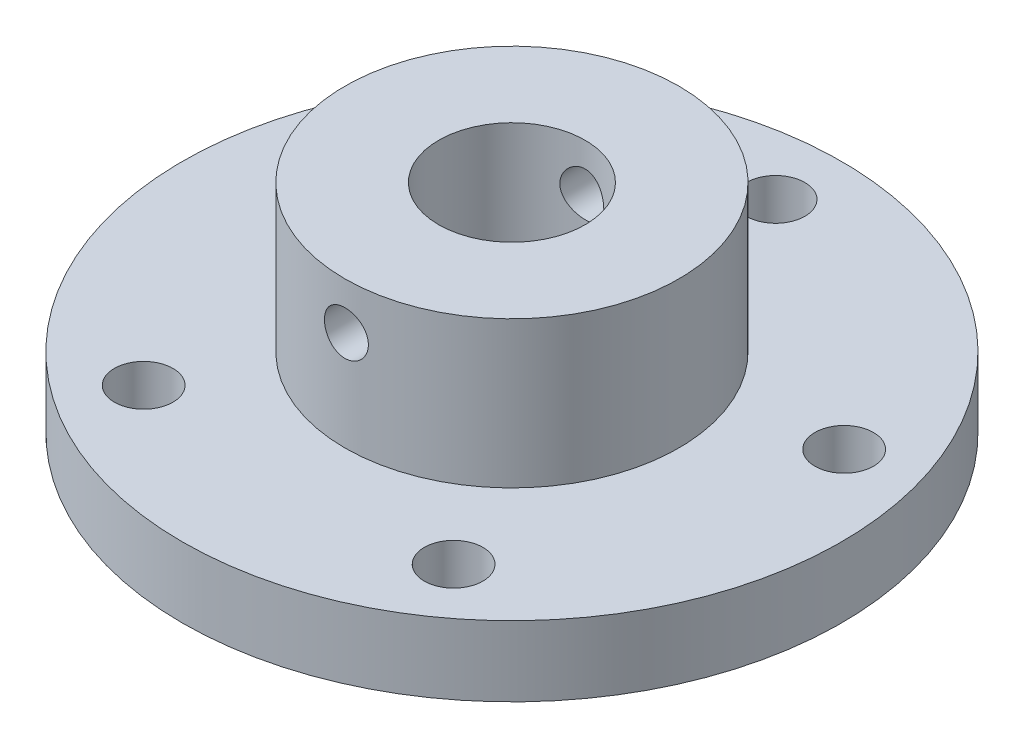
SolidWorks part; units mm, degrees
material "Delrin 2700 NC010, Low Viscosity Acetal Copolymer (SS)"
ref_plane "Front Plane" through (0, 0, 0) normal (0, 0, 1) x (1, 0, 0)
ref_plane "Top Plane" through (0, 0, 0) normal (0, 1, 0) x (1, 0, 0)
ref_plane "Right Plane" through (0, 0, 0) normal (1, 0, 0) x (0, 0, -1)
sketch "Sketch1" plane through (0, 0, 0) normal (0, 0, 1) x (1, 0, 0)
  line L0 (0, 7.8095) -> (0, 0) construction
  line L1 (0, 0) -> (15.875, 0) construction
  line L3 (15.875, 0) -> (71.4375, 0)
  line L4 (15.875, 0) -> (15.875, 15.24)
  line L5 (15.875, 15.24) -> (71.4375, 15.24)
  line L6 (71.4375, 0) -> (71.4375, 15.24)
  line L7 (15.875, 15.24) -> (36.195, 15.24)
  line L8 (15.875, 15.24) -> (15.875, 46.99)
  line L9 (15.875, 46.99) -> (36.195, 46.99)
  line L10 (36.195, 15.24) -> (36.195, 46.99)
  dimension "D1" = 15.875
  dimension "D2" = 15.24
  dimension "D3" = 36.195
  dimension "D4" = 31.75
  dimension "D5" = 71.4375
revolve "Revolve1" add sketch "Sketch1" angle 360 about L0 region at (43.6562, 7.62, 0) region at (26.035, 31.115, 0)
sketch "Sketch2" plane through (0, 15.24, 0) normal (0, 1, 0) x (1, 0, 0)
  line L0 (0, 57.15) -> (54.3529, 17.6603) construction
  line L1 (54.3529, 17.6603) -> (33.5919, -46.2353) construction
  line L2 (33.5919, -46.2353) -> (-33.5919, -46.2353) construction
  line L3 (-33.5919, -46.2353) -> (-54.3529, 17.6603) construction
  line L4 (-54.3529, 17.6603) -> (0, 57.15) construction
  circle A0 centre (0, 0) radius 57.15 construction
  point P3 (-54.3529, 17.6603)
  point P4 (0, 57.15)
  point P5 (54.3529, 17.6603)
  point P6 (-33.5919, -46.2353)
  point P7 (33.5919, -46.2353)
  dimension "D1" = 114.3
hole_wizard "1/2 (0.5) Diameter Hole1" positions "Sketch3" profile "Sketch4" hole size "1/2" standard "ANSI Inch" end condition through all
sketch "Sketch3" plane through (0, 15.24, 0) normal (0, 1, 0) x (1, 0, 0)
  point P0 (-54.3529, 17.6603)
  point P3 (0, 57.15)
  point P6 (54.3529, 17.6603)
  point P9 (33.5919, -46.2353)
  point P12 (-33.5919, -46.2353)
sketch "Sketch4" plane through (-54.3529, 15.24, -17.6603) normal (1, 0, 0) x (0, 0, 1)
  line L0 (0, 0) -> (0, 15.24)
  line L1 (0, 15.24) -> (6.35, 15.24)
  line L2 (6.35, 15.24) -> (6.35, 0)
  line L5 (6.35, 0) -> (0, 0)
  line L11 (0, -6.35) -> (0, 107.95) construction
  dimension "Thru Hole Dia." = 12.7
  dimension "Thru Hole Depth" = 15.24
sketch "Sketch10" plane through (0, 0, 0) normal (0, 0, 1) x (1, 0, 0)
  line L0 (15.875, 46.99) -> (-15.875, 46.99) construction
  circle A0 centre (0, 36.83) radius 4.7625
  dimension "D2" = 9.525
  dimension "D1" = 10.16
extrude "Cut-Extrude1" cut sketch "Sketch10" against normal through all both and the other way through all
